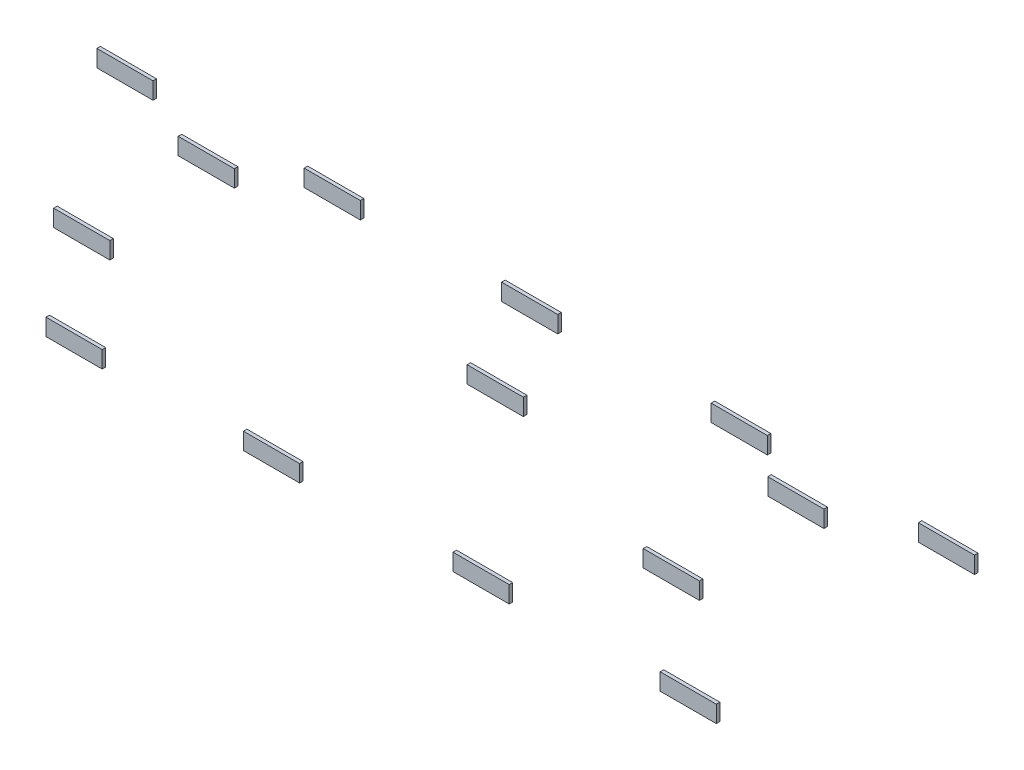
SolidWorks part; units mm, degrees
material "Black Foam Board"
ref_plane "Front Plane" through (0, 0, 0) normal (0, 0, 1) x (1, 0, 0)
ref_plane "Top Plane" through (0, 0, 0) normal (0, 1, 0) x (1, 0, 0)
ref_plane "Right Plane" through (0, 0, 0) normal (1, 0, 0) x (0, 0, -1)
ref_axis "Axis1" through (0, -55, 0) along (0, 1, 0)
sketch "Sketch1" plane through (0, 0, 0) normal (0, 1, 0) x (1, 0, 0)
  line L0 (670.7084, -187.598) -> (-637.6148, -187.598) construction
  line L1 (-15.1245, -182.8355) -> (-15.1245, -187.598)
  line L2 (258.3279, -187.598) -> (-241.8447, -187.598) construction
  line L3 (432.0729, -51.9664) -> (-367.6651, -51.9664) construction
  line L4 (-303.7918, 167.3777) -> (277.3779, 167.3777) construction
  line L5 (432.0729, 116.9436) -> (-367.6651, 116.9436) construction
  line L6 (663.0546, -54.3477) -> (-631.3046, -54.3477) construction
  line L7 (663.0546, 42.1723) -> (-631.3046, 42.1723) construction
  line L8 (-206.7206, -182.8355) -> (-282.9206, -182.8355)
  line L9 (-206.7206, 167.3777) -> (-282.9206, 167.3777)
  line L10 (-206.7206, 167.3777) -> (-206.7206, 162.6152)
  line L11 (-206.7206, 162.6152) -> (-282.9206, 162.6152)
  line L12 (-282.9206, 167.3777) -> (-282.9206, 162.6152)
  line L13 (-206.7206, 167.3777) -> (-282.9206, 162.6152) construction
  line L14 (-206.7206, 162.6152) -> (-282.9206, 167.3777) construction
  line L15 (-206.7206, -182.8355) -> (-206.7206, -187.598)
  line L16 (-206.7206, -187.598) -> (-282.9206, -187.598)
  line L17 (-282.9206, -182.8355) -> (-282.9206, -187.598)
  line L18 (-206.7206, -182.8355) -> (-282.9206, -187.598) construction
  line L19 (-206.7206, -187.598) -> (-282.9206, -182.8355) construction
  line L24 (-487.9393, 167.3777) -> (-564.1393, 167.3777)
  line L26 (345.4227, 167.3777) -> (269.2227, 167.3777)
  line L27 (345.4227, 167.3777) -> (345.4227, 162.6152)
  line L28 (345.4227, 162.6152) -> (269.2227, 162.6152)
  line L29 (269.2227, 167.3777) -> (269.2227, 162.6152)
  line L30 (345.4227, 167.3777) -> (269.2227, 162.6152) construction
  line L31 (345.4227, 162.6152) -> (269.2227, 167.3777) construction
  line L32 (61.0755, 167.3777) -> (-15.1245, 167.3777)
  line L33 (61.0755, 167.3777) -> (61.0755, 162.6152)
  line L34 (61.0755, 162.6152) -> (-15.1245, 162.6152)
  line L35 (-15.1245, 167.3777) -> (-15.1245, 162.6152)
  line L36 (61.0755, 167.3777) -> (-15.1245, 162.6152) construction
  line L37 (61.0755, 162.6152) -> (-15.1245, 167.3777) construction
  line L38 (626.3532, 167.3777) -> (550.1532, 167.3777)
  line L39 (626.3532, 167.3777) -> (626.3532, 162.6152)
  line L40 (626.3532, 162.6152) -> (550.1532, 162.6152)
  line L41 (550.1532, 167.3777) -> (550.1532, 162.6152)
  line L42 (626.3532, 167.3777) -> (550.1532, 162.6152) construction
  line L43 (626.3532, 162.6152) -> (550.1532, 167.3777) construction
  line L50 (345.4227, -182.8355) -> (269.2227, -182.8355)
  line L51 (345.4227, -182.8355) -> (345.4227, -187.598)
  line L52 (345.4227, -187.598) -> (269.2227, -187.598)
  line L53 (269.2227, -182.8355) -> (269.2227, -187.598)
  line L54 (345.4227, -182.8355) -> (269.2227, -187.598) construction
  line L55 (345.4227, -187.598) -> (269.2227, -182.8355) construction
  line L56 (626.3532, -182.8355) -> (550.1532, -182.8355)
  line L57 (626.3532, -182.8355) -> (626.3532, -187.598)
  line L58 (626.3532, -187.598) -> (550.1532, -187.598)
  line L59 (550.1532, -182.8355) -> (550.1532, -187.598)
  line L60 (626.3532, -182.8355) -> (550.1532, -187.598) construction
  line L61 (626.3532, -187.598) -> (550.1532, -182.8355) construction
  line L62 (61.0755, -182.8355) -> (-15.1245, -182.8355)
  line L63 (61.0755, -182.8355) -> (61.0755, -187.598)
  line L64 (61.0755, -187.598) -> (-15.1245, -187.598)
  line L66 (61.0755, -182.8355) -> (-15.1245, -187.598) construction
  line L67 (61.0755, -187.598) -> (-15.1245, -182.8355) construction
  line L68 (470.1729, 119.3248) -> (393.9729, 119.3248)
  line L69 (470.1729, 119.3248) -> (470.1729, 114.5623)
  line L70 (470.1729, 114.5623) -> (393.9729, 114.5623)
  line L71 (393.9729, 119.3248) -> (393.9729, 114.5623)
  line L72 (470.1729, 119.3248) -> (393.9729, 114.5623) construction
  line L73 (470.1729, 114.5623) -> (393.9729, 119.3248) construction
  line L74 (470.1729, -49.5852) -> (393.9729, -49.5852)
  line L75 (470.1729, -49.5852) -> (470.1729, -54.3477)
  line L76 (470.1729, -54.3477) -> (393.9729, -54.3477)
  line L77 (393.9729, -49.5852) -> (393.9729, -54.3477)
  line L78 (470.1729, -49.5852) -> (393.9729, -54.3477) construction
  line L79 (470.1729, -54.3477) -> (393.9729, -49.5852) construction
  line L80 (134.8121, 46.9348) -> (58.6121, 46.9348)
  line L81 (134.8121, 46.9348) -> (134.8121, 42.1723)
  line L82 (134.8121, 42.1723) -> (58.6121, 42.1723)
  line L83 (58.6121, 46.9348) -> (58.6121, 42.1723)
  line L84 (134.8121, 46.9348) -> (58.6121, 42.1723) construction
  line L85 (134.8121, 42.1723) -> (58.6121, 46.9348) construction
  line L86 (-329.5651, 119.3248) -> (-405.7651, 119.3248)
  line L87 (-329.5651, 119.3248) -> (-329.5651, 114.5623)
  line L88 (-329.5651, 114.5623) -> (-405.7651, 114.5623)
  line L89 (-405.7651, 119.3248) -> (-405.7651, 114.5623)
  line L90 (-329.5651, 119.3248) -> (-405.7651, 114.5623) construction
  line L91 (-329.5651, 114.5623) -> (-405.7651, 119.3248) construction
  line L92 (-329.5651, -49.5852) -> (-405.7651, -49.5852)
  line L93 (-329.5651, -49.5852) -> (-329.5651, -54.3477)
  line L94 (-329.5651, -54.3477) -> (-405.7651, -54.3477)
  line L95 (-405.7651, -49.5852) -> (-405.7651, -54.3477)
  line L96 (-329.5651, -49.5852) -> (-405.7651, -54.3477) construction
  line L97 (-329.5651, -54.3477) -> (-405.7651, -49.5852) construction
  line L98 (663.0546, 114.5623) -> (-631.3046, 114.5623) construction
  line L99 (-631.3046, 167.3777) -> (663.0546, 167.3777) construction
  line L103 (-487.9393, 167.3777) -> (-487.9393, 162.6152)
  line L104 (-487.9393, 162.6152) -> (-564.1393, 162.6152)
  line L105 (-564.1393, 167.3777) -> (-564.1393, 162.6152)
  line L106 (-487.9393, 167.3777) -> (-564.1393, 162.6152) construction
  line L107 (-487.9393, 162.6152) -> (-564.1393, 167.3777) construction
  ellipse E5 centre (277.3779, 63.0341) end of major axis (277.3779, -41.3094) minor radius 3.429 (278.4021, 162.6152) -> (277.3779, 167.3777) ccw construction
  point P32 (-526.0393, 164.9964)
  point P56 (-244.8206, 164.9964)
  point P61 (-244.8206, -185.2168)
  point P66 (-310.5667, 159.7235)
  point P71 (307.3227, 164.9964)
  point P76 (22.9755, 164.9964)
  point P81 (588.2532, 164.9964)
  point P91 (307.3227, -185.2168)
  point P96 (588.2532, -185.2168)
  point P101 (22.9755, -185.2168)
  point P106 (432.0729, 116.9436)
  point P111 (432.0729, -51.9664)
  point P116 (96.7121, 44.5536)
  point P121 (-367.6651, 116.9436)
  point P126 (-367.6651, -51.9664)
  dimension "D1" = 4.7625
  dimension "D2" = 76.2
  dimension "D3" = 432.0729
  dimension "D4" = 96.7121
  dimension "D5" = 799.738
extrude "Boss-Extrude1" add sketch "Sketch1" against normal blind 22.86
